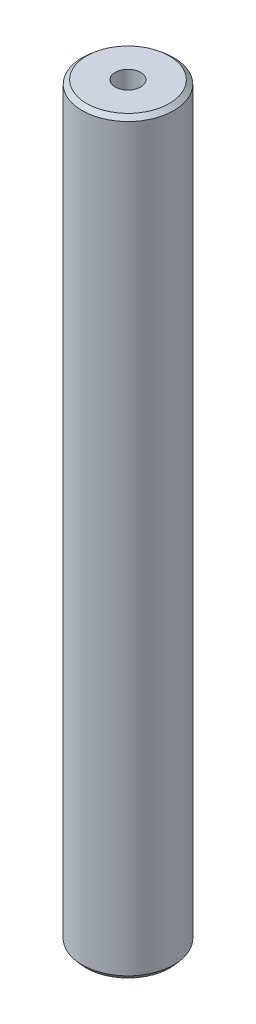
SolidWorks part; units mm, degrees
ref_plane "Front Plane" through (0, 0, 0) normal (0, 0, 1) x (1, 0, 0)
ref_plane "Top Plane" through (0, 0, 0) normal (0, 1, 0) x (1, 0, 0)
ref_plane "Right Plane" through (0, 0, 0) normal (1, 0, 0) x (0, 0, -1)
sketch "Sketch1" plane through (0, 0, 0) normal (0, 1, 0) x (1, 0, 0)
  circle A0 centre (0, 0) radius 7.5
  dimension "SHAFT_OD" = 15
extrude "Boss-Extrude1" add sketch "Sketch1" along normal blind 122.4141
sketch "Sketch2" plane through (0, 0, 0) normal (0, 1, 0) x (1, 0, 0)
  circle A0 centre (0, 0) radius 2.0862
  dimension "BORE_D" = 4.1724
extrude "Cut-Extrude1" cut sketch "Sketch2" along normal through all
chamfer "Chamfer1" distance 0.6283 angle 49.982 2 edges at (0, 122.4141, 7.5) (0, 0, 7.5) first distance on face at (0, 122.4141, 7.5) first distance on face at (0, 0, 2.0862)
